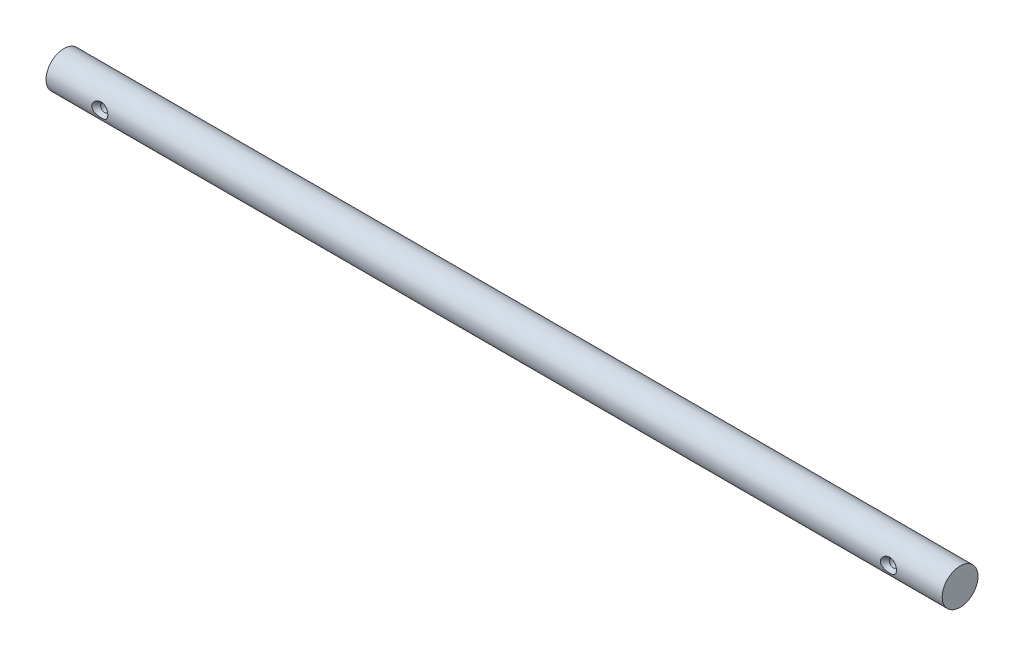
SolidWorks part; units mm, degrees
ref_plane "Front Plane" through (0, 0, 0) normal (0, 0, 1) x (1, 0, 0)
ref_plane "Top Plane" through (0, 0, 0) normal (0, 1, 0) x (1, 0, 0)
ref_plane "Right Plane" through (0, 0, 0) normal (1, 0, 0) x (0, 0, -1)
ref_axis "Axis1" through (88.99, 0, 0) along (-1, 0, 0)
sketch "Sketch1" plane through (0, 0, 0) normal (0, 0, 1) x (1, 0, 0)
  line L0 (0, 0) -> (317.5, 0)
  line L1 (55, 0) -> (-55, 0) construction
  line L2 (317.5, 0) -> (317.5, 6.35)
  line L3 (317.5, 6.35) -> (0, 6.35)
  line L4 (0, -55) -> (0, 55) construction
  line L5 (0, 6.35) -> (0, 0)
  dimension "D1" = 317.5
  dimension "D2" = 6.35
revolve "Revolve1" add sketch "Sketch1" angle 360 about L0
ref_plane "Plane1" through (0, 0, 6.35) normal (0, 0, 1) x (1, 0, 0)
ref_plane "Plane2" through (19.05, 0, 0) normal (1, 0, 0) x (0, 0, -1)
ref_plane "Plane3" through (298.45, 0, 0) normal (1, 0, 0) x (0, 0, -1)
ref_axis "Axis2" through (19.05, 0, -45.2091) along (0, 0, 1)
ref_axis "Axis3" through (298.45, 0, 64.0767) along (0, 0, -1)
hole_wizard "CSK for #4 Flat Head Machine Screw (100)1" positions "Sketch2" profile "Sketch4" countersink size "#4" standard "ANSI Inch" end condition through all
sketch "Sketch2" plane through (0, 0, 6.35) normal (0, 0, 1) x (1, 0, 0)
  point P0 (19.05, 0)
  point P2 (298.45, 0)
sketch "Sketch4" plane through (19.05, 0, 6.35) normal (1, 0, 0) x (0, -1, 0)
  line L0 (0, 0) -> (0, 12.7)
  line L1 (0, 12.7) -> (1.3891, 12.7)
  line L2 (1.3891, 12.7) -> (1.3891, 1.6892)
  line L3 (1.3891, 1.6892) -> (2.8575, 0)
  line L5 (2.8575, 0) -> (0, 0)
  line L6 (-1.3891, 1.6892) -> (-2.8575, 0) construction
  line L11 (0, -6.35) -> (0, 107.95) construction
  dimension "Thru Hole Dia." = 2.7781
  dimension "Thru Hole Depth" = 12.7
  dimension "Near C'Sink Dia." = 5.715
  dimension "Near C'Sink Angle" = 82
ref_plane "Plane4" through (0, 0, -6.35) normal (0, 0, -1) x (-1, 0, 0)
